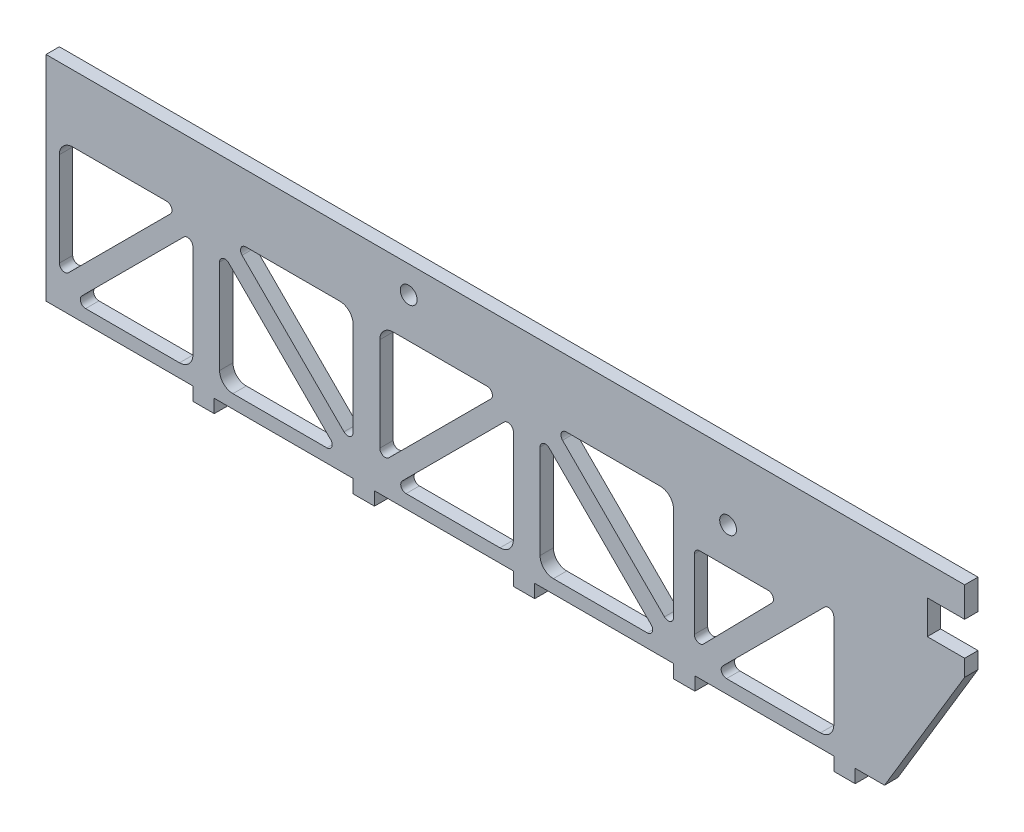
SolidWorks part; units mm, degrees
material "Pine"
ref_plane "Front Plane" through (0, 0, 0) normal (0, 0, 1) x (1, 0, 0)
ref_plane "Top Plane" through (0, 0, 0) normal (0, 1, 0) x (1, 0, 0)
ref_plane "Right Plane" through (0, 0, 0) normal (1, 0, 0) x (0, 0, -1)
sketch "Model" plane through (0, 0, 0) normal (0, 0, 1) x (1, 0, 0)
  line L0 (312.6855, 15.1239) -> (345.2281, 48.2988)
  line L1 (343.4149, 52.6175) -> (310.8722, 52.6175)
  line L2 (308.3322, 50.0775) -> (308.3322, 16.9026)
  line L8 (171.2321, 6.35) -> (215.9, 6.35)
  line L9 (217.9139, 59.1639) -> (169.4361, 10.6861)
  line L10 (222.25, 57.3679) -> (222.25, 12.7)
  line L11 (234.95, 57.3679) -> (234.95, 12.7)
  line L12 (239.2861, 59.1639) -> (287.7639, 10.6861)
  line L13 (241.3, 6.35) -> (285.9679, 6.35)
  line L14 (294.1139, 17.0361) -> (245.6361, 65.5139)
  line L15 (247.4321, 69.85) -> (292.1, 69.85)
  line L16 (298.45, 63.5) -> (298.45, 18.8321)
  line L17 (323.6321, 6.35) -> (368.3, 6.35)
  line L18 (370.3139, 59.1639) -> (321.8361, 10.6861)
  line L19 (374.65, 57.3679) -> (374.65, 12.7)
  line L20 (18.8321, 6.35) -> (63.5, 6.35)
  line L21 (17.0361, 10.6861) -> (65.5139, 59.1639)
  line L22 (69.85, 57.3679) -> (69.85, 12.7)
  line L23 (82.55, 57.3679) -> (82.55, 12.7)
  line L24 (86.8861, 59.1639) -> (135.3639, 10.6861)
  line L25 (88.9, 6.35) -> (133.5679, 6.35)
  line L26 (93.2361, 65.5139) -> (141.7139, 17.0361)
  line L27 (95.0321, 69.85) -> (139.7, 69.85)
  line L28 (146.05, 63.5) -> (146.05, 18.8321)
  line L29 (163.0861, 17.0361) -> (211.5639, 65.5139)
  line L30 (158.75, 63.5) -> (158.75, 18.8321)
  line L31 (165.1, 69.85) -> (209.7679, 69.85)
  line L35 (419.1, 87.376) -> (419.1, 71.374)
  line L36 (436.88, 87.376) -> (419.1, 87.376)
  line L37 (436.88, 87.376) -> (436.88, 95.25)
  line L38 (0, 95.25) -> (436.88, 95.25)
  line L39 (0, 0) -> (0, 95.25)
  line L40 (0, 0) -> (398.78, 0)
  line L41 (436.88, 63.5) -> (398.78, 0)
  line L42 (436.88, 63.5) -> (436.88, 71.374)
  line L43 (419.1, 71.374) -> (436.88, 71.374)
  line L44 (6.35, 63.5) -> (6.35, 18.8321)
  line L45 (12.7, 69.85) -> (57.3679, 69.85)
  line L46 (59.1639, 65.5139) -> (10.6861, 17.0361)
  arc A0 (215.9, 6.35) -> (222.25, 12.7) centre (215.9, 12.7) ccw
  arc A1 (169.4361, 10.6861) -> (171.2321, 6.35) centre (171.2321, 8.89) ccw
  arc A2 (222.25, 57.3679) -> (217.9139, 59.1639) centre (219.71, 57.3679) ccw
  arc A3 (239.2861, 59.1639) -> (234.95, 57.3679) centre (237.49, 57.3679) ccw
  arc A4 (285.9679, 6.35) -> (287.7639, 10.6861) centre (285.9679, 8.89) ccw
  arc A5 (234.95, 12.7) -> (241.3, 6.35) centre (241.3, 12.7) ccw
  arc A6 (247.4321, 69.85) -> (245.6361, 65.5139) centre (247.4321, 67.31) ccw
  arc A7 (298.45, 63.5) -> (292.1, 69.85) centre (292.1, 63.5) ccw
  arc A8 (294.1139, 17.0361) -> (298.45, 18.8321) centre (295.91, 18.8321) ccw
  arc A9 (321.8361, 10.6861) -> (323.6321, 6.35) centre (323.6321, 8.89) ccw
  arc A10 (374.65, 57.3679) -> (370.3139, 59.1639) centre (372.11, 57.3679) ccw
  arc A11 (368.3, 6.35) -> (374.65, 12.7) centre (368.3, 12.7) ccw
  arc A12 (63.5, 6.35) -> (69.85, 12.7) centre (63.5, 12.7) ccw
  arc A13 (17.0361, 10.6861) -> (18.8321, 6.35) centre (18.8321, 8.89) ccw
  arc A14 (69.85, 57.3679) -> (65.5139, 59.1639) centre (67.31, 57.3679) ccw
  arc A15 (86.8861, 59.1639) -> (82.55, 57.3679) centre (85.09, 57.3679) ccw
  arc A16 (133.5679, 6.35) -> (135.3639, 10.6861) centre (133.5679, 8.89) ccw
  arc A17 (82.55, 12.7) -> (88.9, 6.35) centre (88.9, 12.7) ccw
  arc A18 (95.0321, 69.85) -> (93.2361, 65.5139) centre (95.0321, 67.31) ccw
  arc A19 (146.05, 63.5) -> (139.7, 69.85) centre (139.7, 63.5) ccw
  arc A20 (141.7139, 17.0361) -> (146.05, 18.8321) centre (143.51, 18.8321) ccw
  arc A21 (158.75, 18.8321) -> (163.0861, 17.0361) centre (161.29, 18.8321) ccw
  arc A22 (165.1, 69.85) -> (158.75, 63.5) centre (165.1, 63.5) ccw
  arc A23 (211.5639, 65.5139) -> (209.7679, 69.85) centre (209.7679, 67.31) ccw
  arc A24 (345.2281, 48.2988) -> (343.4149, 52.6175) centre (343.4149, 50.0775) ccw
  arc A25 (310.8722, 52.6175) -> (308.3322, 50.0775) centre (310.8722, 50.0775) ccw
  arc A26 (312.6855, 15.1239) -> (308.3322, 16.9026) centre (310.8722, 16.9026) cw
  arc A27 (6.35, 18.8321) -> (10.6861, 17.0361) centre (8.89, 18.8321) ccw
  arc A28 (12.7, 69.85) -> (6.35, 63.5) centre (12.7, 63.5) ccw
  arc A29 (59.1639, 65.5139) -> (57.3679, 69.85) centre (57.3679, 67.31) ccw
  circle A30 centre (172.4917, 88.8013) radius 4
  circle A31 centre (324.3837, 70.0053) radius 4
  dimension "D2" = 6.4487
  dimension "D3" = 172.4917
  dimension "D4" = 8
  dimension "D5" = 18.796
  dimension "D6" = 8
  dimension "D8" = 2.54
  dimension "D1" = 95.25
  dimension "D7" = 151.892
extrude "Boss-Extrude2" add sketch "Model" along normal blind 6.35
sketch "Sketch1" plane through (0, 0, 6.35) normal (0, 0, 1) x (1, 0, 0)
  line L0 (69.85, 12.7) -> (69.85, 0) construction
  line L1 (146.05, 95.25) -> (146.05, 0) construction
  line L2 (146.05, 18.8321) -> (146.05, 63.5) construction
  line L3 (0, 0) -> (398.78, 0) construction
  line L4 (222.25, 95.25) -> (222.25, 0) construction
  line L5 (222.25, 12.7) -> (222.25, 57.3679) construction
  line L6 (298.45, 18.8321) -> (298.45, 0) construction
  line L7 (146.05, 0) -> (156.21, 0)
  line L8 (69.85, 0) -> (80.01, 0)
  line L9 (69.85, 0) -> (69.85, -6.35)
  line L10 (69.85, -6.35) -> (80.01, -6.35)
  line L11 (80.01, 0) -> (80.01, -6.35)
  line L16 (222.25, 0) -> (232.41, 0)
  line L17 (222.25, 0) -> (222.25, -6.35)
  line L18 (222.25, -6.35) -> (232.41, -6.35)
  line L19 (232.41, 0) -> (232.41, -6.35)
  line L20 (146.05, 0) -> (146.05, -6.35)
  line L21 (146.05, -6.35) -> (156.21, -6.35)
  line L22 (156.21, 0) -> (156.21, -6.35)
  line L24 (374.65, 12.7) -> (374.65, 0) construction
  line L25 (374.65, 12.7) -> (374.65, 57.3679) construction
  line L27 (298.45, 0) -> (308.61, 0)
  line L28 (298.45, 0) -> (298.45, -6.35)
  line L29 (298.45, -6.35) -> (308.61, -6.35)
  line L30 (308.61, 0) -> (308.61, -6.35)
  line L31 (374.65, 0) -> (384.81, 0)
  line L32 (374.65, 0) -> (374.65, -6.35)
  line L33 (374.65, -6.35) -> (384.81, -6.35)
  line L34 (384.81, 0) -> (384.81, -6.35)
  line L39 (0, 101.6) -> (436.88, 101.6)
  line L53 (0, 95.25) -> (0, 101.6)
  line L55 (436.88, 95.25) -> (436.88, 101.6)
  line L56 (436.88, 95.25) -> (0, 95.25) construction
  line L57 (0, 95.25) -> (436.88, 95.25)
  arc A0 (368.3, 6.35) -> (374.65, 12.7) centre (368.3, 12.7) ccw construction
  dimension "D1" = 10.16
  dimension "D2" = 6.35
  dimension "D3" = 10.16
  dimension "D4" = 6.35
  dimension "D5" = 10.16
  dimension "D6" = 10.16
  dimension "D7" = 10.16
  dimension "D13" = 6.35
extrude "Boss-Extrude3" add sketch "Sketch1" against normal up to surface (6.35 mm away) up to face at (321.5295, 39.2174, 0)
